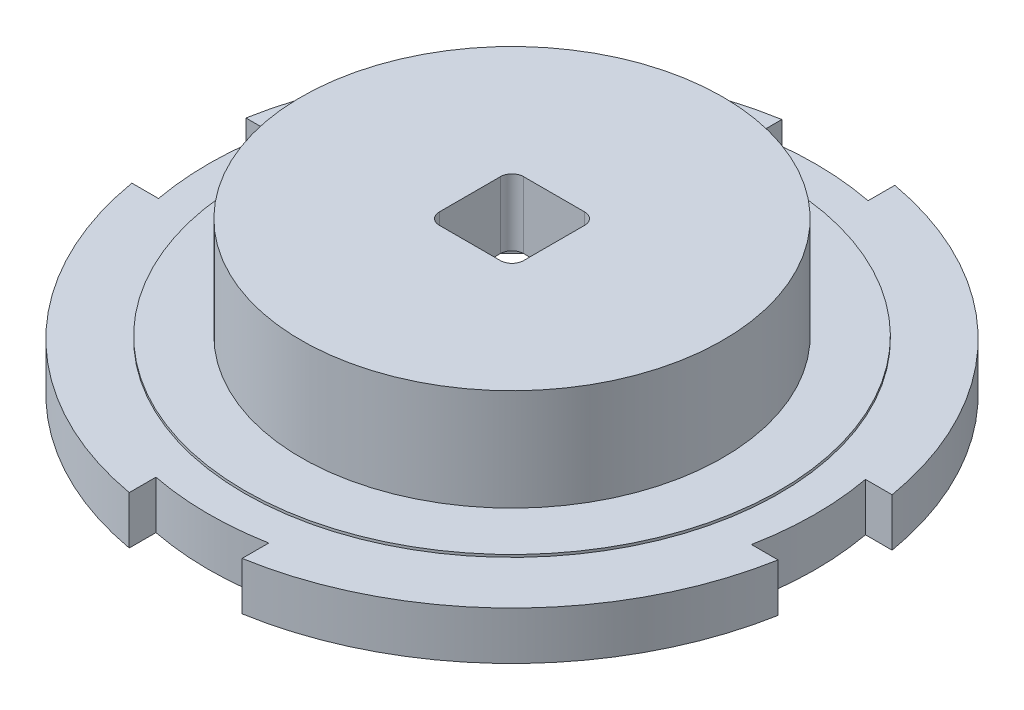
SolidWorks part; units mm, degrees
note: '?' marks a value the reader was unsure of.
ref_plane "Front Plane" through (0, 0, 0) normal (0, 0, 1) x (1, 0, 0)
ref_plane "Top Plane" through (0, 0, 0) normal (0, 1, 0) x (1, 0, 0)
ref_plane "Right Plane" through (0, 0, 0) normal (1, 0, 0) x (0, 0, -1)
sketch "Sketch1" plane through (0, 0, 0) normal (0, 1, 0) x (1, 0, 0)
  line L0 (35.4054, 6.5405) -> (38.5653, 6.5405)
  line L1 (35.3329, -6.9215) -> (38.4988, -6.9215)
  line L2 (-55, 0) -> (55, 0) construction
  line L3 (6.5405, -35.4054) -> (6.5405, -38.5653)
  line L4 (-6.9215, -35.3329) -> (-6.9215, -38.4988)
  line L5 (-35.4054, -6.5405) -> (-38.5653, -6.5405)
  line L6 (-35.3329, 6.9215) -> (-38.4988, 6.9215)
  line L7 (-6.5405, 35.4054) -> (-6.5405, 38.5653)
  line L8 (6.9215, 35.3329) -> (6.9215, 38.4988)
  line L9 (-5, 5) -> (-5, -5)
  line L10 (-5, -5) -> (5, -5)
  line L11 (5, -5) -> (5, 5)
  line L12 (5, 5) -> (-5, 5)
  line L13 (0, -55) -> (0, 55) construction
  arc A1 (-38.5653, -6.5405) -> (-6.9215, -38.4988) centre (0, 0) ccw
  arc A3 (-35.3329, 6.9215) -> (-35.4054, -6.5405) centre (0, 0) ccw
  arc A4 (6.9215, 35.3329) -> (-6.5405, 35.4054) centre (0, 0) ccw
  arc A5 (35.3329, -6.9215) -> (35.4054, 6.5405) centre (0, 0) ccw
  arc A6 (-6.9215, -35.3329) -> (6.5405, -35.4054) centre (0, 0) ccw
  arc A7 (6.5405, -38.5653) -> (38.4988, -6.9215) centre (0, 0) ccw
  arc A8 (38.5653, 6.5405) -> (6.9215, 38.4988) centre (0, 0) ccw
  arc A9 (-6.5405, 38.5653) -> (-38.4988, 6.9215) centre (0, 0) ccw
  point P11 (0, 5)
  point P26 (0, 0)
  point P28 (5, 0)
  dimension "D1" = 78.232
  dimension "D2" = 72.009
  dimension "D6" = 10
  dimension "D3" = 13.462
  dimension "D4" = 6.5405
  dimension "D7" = 10
  dimension "D5" = 4
ref_axis "Axis1" through (41.0751, 0, 0) along (-1, 0, 0)?
ref_plane "Plane2" through (0, 0, 0) normal (0, -0.9903, 0.1392) x (-1, 0, 0)
ref_plane "Plane3" through (0, 6.2882, -0.8837) normal (0, -0.9903, 0.1392) x (-1, 0, 0)
extrude "Boss-Extrude2" add sketch "Sketch1" along normal blind 6
sketch "Sketch2" plane through (0, 0, 0) normal (0, -1, 0) x (1, 0, 0)
  line L3 (17.3777, -10.033) -> (-0.2866, -40.6283)
  line L4 (-4.5397, -40.3749) -> (8.1962, -18.3157)
  line L5 (3.2131, 0) -> (-3.2131, 0) construction
  arc A3 (8.1962, -18.3157) -> (17.3777, -10.033) centre (0, 0) cw
  arc A4 (-0.2866, -40.6283) -> (-4.5397, -40.3749) centre (0, 0) cw
  point P4 (8.5456, -25.3307)
  dimension "D1" = 20.066
  dimension "D2" = 3.81
  dimension "D3" = 60
extrude "Cut-Extrude1" cut sketch "Sketch2" against normal blind 3.81
sketch "Sketch3" plane through (0, 0, 0) normal (0, -1, 0) x (1, 0, 0)
  circle A0 centre (0, 0) radius 31.75
extrude "Cut-Extrude2" cut sketch "Sketch3" against normal blind 0.3
sketch "Sketch4" plane through (0, 6, 0) normal (0, 1, 0) x (1, 0, 0)
  circle A0 centre (0, 0) radius 25.019
  dimension "D1" = 50.038
extrude "Boss-Extrude3" add sketch "Sketch4" along normal blind 12.065
sketch "Sketch5" plane through (0, 3.81, 0) normal (0, -1, 0) x (1, 0, 0)
  circle A0 centre (0, 0) radius 15.875
extrude "Cut-Extrude3" cut sketch "Sketch5" against normal blind 6.35
fillet "Fillet1" radius 1.3716 4 edges at (5, 14.1125, -5) (5, 14.1125, 5) (-5, 14.1125, 5) (-5, 14.1125, -5)
sketch "Sketch6" plane through (0, 6, 0) normal (0, 1, 0) x (1, 0, 0)
  circle A0 centre (0, 0) radius 31.75
  circle A1 centre (0, 0) radius 54.9701
  dimension "D1" = 63.5
extrude "Cut-Extrude4" cut sketch "Sketch6" against normal blind 0.3
